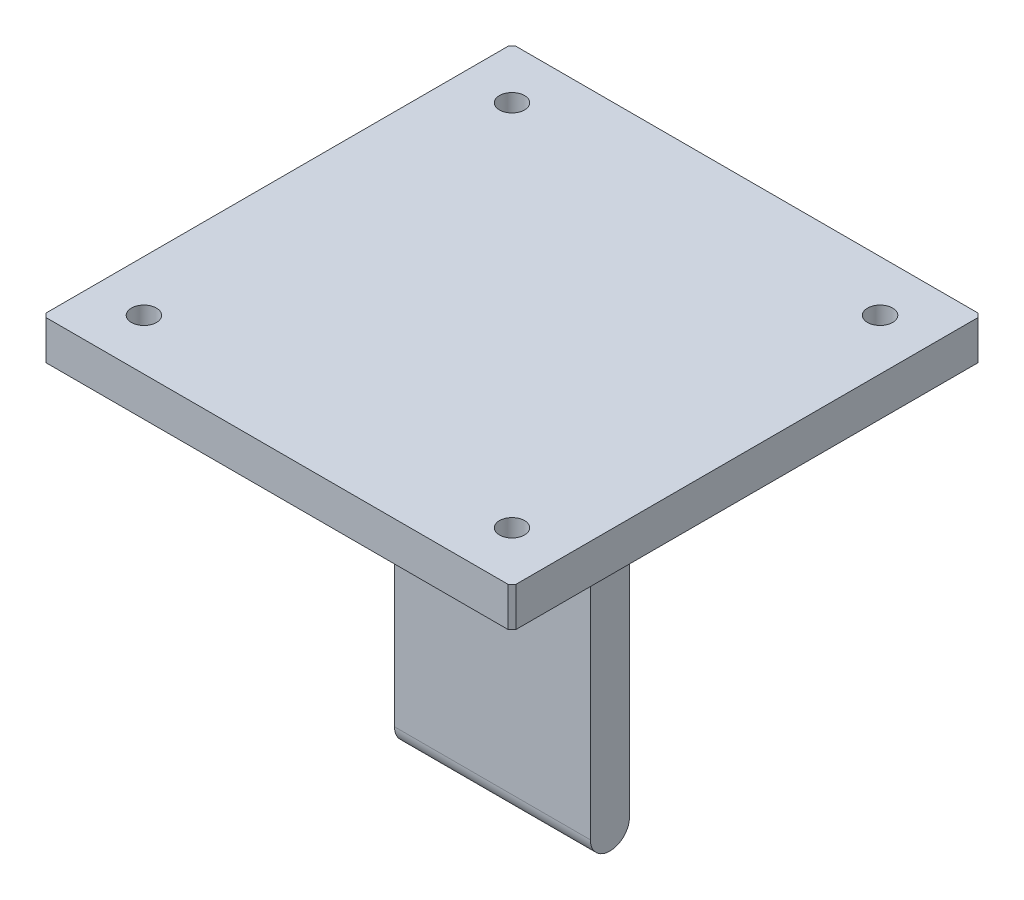
SolidWorks part; units mm, degrees
ref_plane "Ebene vorne" through (0, 0, 0) normal (0, 0, 1) x (1, 0, 0)
ref_plane "Ebene oben" through (0, 0, 0) normal (0, 1, 0) x (1, 0, 0)
ref_plane "Ebene rechts" through (0, 0, 0) normal (1, 0, 0) x (0, 0, -1)
sketch "Skizze1" plane through (0, 0, 0) normal (0, 1, 0) x (1, 0, 0)
  line L1 (0, 0) -> (50, 0) construction
  line L2 (0, 0) -> (0, 60) construction
  line L3 (0, 60) -> (50, 60) construction
  line L4 (50, 0) -> (50, 60) construction
  line L5 (10, 55) -> (40, 55) construction
  line L6 (10, 55) -> (10, 5) construction
  line L7 (10, 5) -> (40, 5) construction
  line L8 (40, 55) -> (40, 5) construction
  line L9 (-5, 0) -> (55, 0)
  line L10 (-5, 0) -> (-5, 60)
  line L11 (-5, 60) -> (55, 60)
  line L12 (55, 0) -> (55, 60)
  point P9 (10, 30)
  point P10 (0, 30)
  point P11 (25, 55)
  point P12 (25, 60)
  point P13 (25, 30)
  point P19 (55, 30)
  point P20 (25, 60)
  dimension "D5" = 60
  dimension "D1" = 50
  dimension "D2" = 60
  dimension "D3" = 10
  dimension "D4" = 5
extrude "Aufsatz-Linear austragen1" add sketch "Skizze1" along normal blind 5
sketch "Skizze7" plane through (0, 5, 0) normal (0, 1, 0) x (1, 0, 0)
  line L1 (5, 10) -> (45, 10) construction
  line L2 (5, 10) -> (5, 50) construction
  line L3 (5, 50) -> (45, 50) construction
  line L4 (45, 10) -> (45, 50) construction
  line L5 (5, 10) -> (45, 50) construction
  line L6 (5, 50) -> (45, 10) construction
  line L7 (1.5, 53.5) -> (1.5, 6.5) construction
  line L8 (48.5, 53.5) -> (48.5, 6.5) construction
  line L10 (48.5, 6.5) -> (1.5, 6.5) construction
  line L11 (1.5, 53.5) -> (48.5, 53.5) construction
  circle A0 centre (1.5, 53.5) radius 1.6
  circle A1 centre (48.5, 53.5) radius 1.6
  circle A2 centre (48.5, 6.5) radius 1.6
  circle A3 centre (1.5, 6.5) radius 1.6
  point P0 (25, 30)
  point P5 (25, 53.5)
  point P10 (48.5, 30)
  dimension "D4" = 3.2
  dimension "D1" = 47
  dimension "D2" = 40
  dimension "D3" = 47
extrude "Schnitt-Linear austragen1" cut sketch "Skizze7" against normal blind 10 contours A2 | A1 | A0 | A3
chamfer "Fase1" distance 0.5 angle 45 4 edges at (-5, 2.5, 0) (55, 2.5, 0) (55, 2.5, -60) (-5, 2.5, -60)
sketch "Skizze8" plane through (0, 0, 0) normal (0, -1, 0) x (1, 0, 0)
  line L0 (55, -30) -> (37.5, -30) construction
  line L1 (12.5, -27.5) -> (37.5, -27.5)
  line L2 (12.5, -27.5) -> (12.5, -32.5)
  line L3 (12.5, -32.5) -> (37.5, -32.5)
  line L4 (37.5, -27.5) -> (37.5, -32.5)
  line L5 (55, -0.5) -> (55, -59.5) construction
  line L6 (25, -27.5) -> (25, 0) construction
  line L7 (-4.5, 0) -> (54.5, 0) construction
  dimension "D1" = 5
  dimension "D2" = 25
extrude "Aufsatz-Linear austragen2" add sketch "Skizze8" along normal blind 48
fillet "Verrundung3" radius 2.5 2 edges at (25, -48, -32.5) (25, -48, -27.5)
